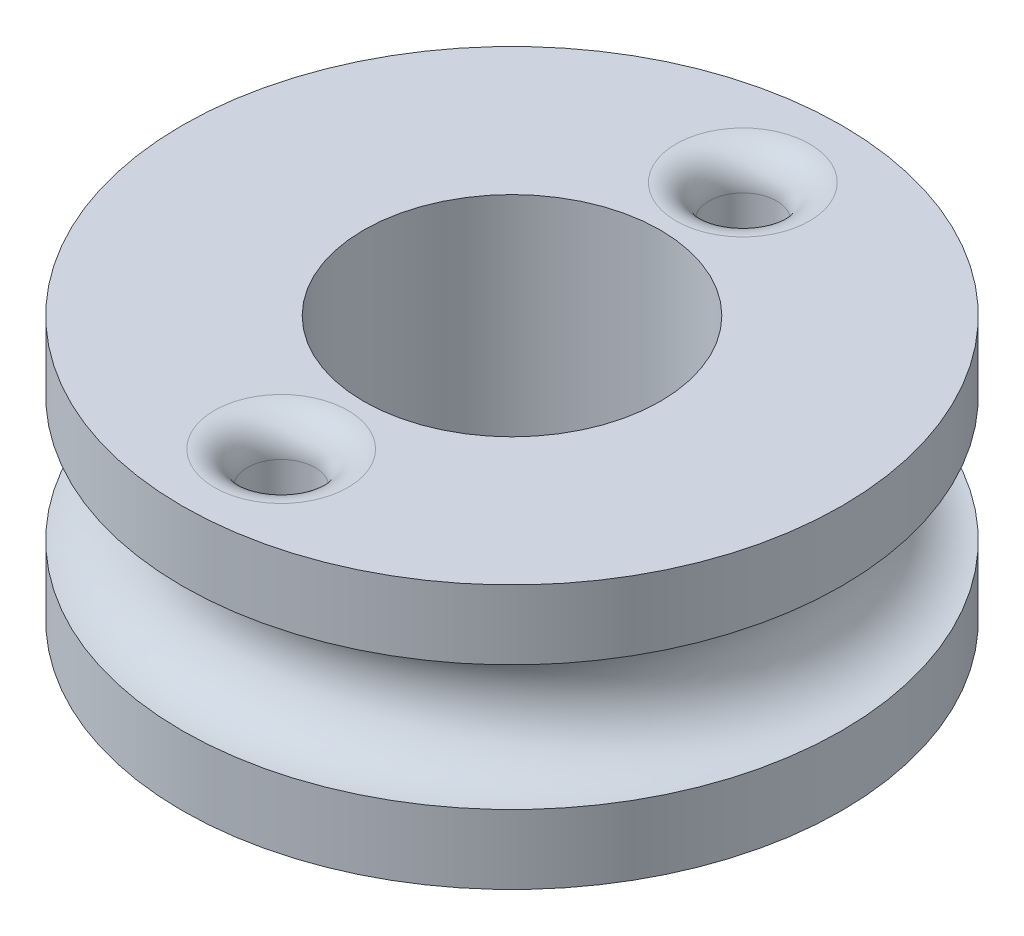
SolidWorks part; units mm, degrees
ref_plane "Front Plane" through (0, 0, 0) normal (0, 0, 1) x (1, 0, 0)
ref_plane "Top Plane" through (0, 0, 0) normal (0, 1, 0) x (1, 0, 0)
ref_plane "Right Plane" through (0, 0, 0) normal (1, 0, 0) x (0, 0, -1)
sketch "Sketch1" plane through (0, 0, 0) normal (0, 1, 0) x (1, 0, 0)
  circle A0 centre (0, 0) radius 10
  circle A1 centre (0, 0) radius 4.5
  dimension "D1" = 20
  dimension "D2" = 9
extrude "Boss-Extrude1" add sketch "Sketch1" along normal blind 8
sketch "Sketch3" plane through (0, 0, 0) normal (0, 0, 1) x (1, 0, 0)
  line L0 (0, -0.9519) -> (0, 8.8261) construction
  line L1 (-17.7863, 4) -> (10.4979, 4) construction
  line L2 (-10, 8) -> (-10, 0) construction
  circle A0 centre (-10, 4) radius 1.9
  point P5 (-10, 4)
  dimension "D1" = 3.8
revolve "Cut-Revolve1" cut sketch "Sketch3" angle 360 about L0
sketch "Sketch4" plane through (0, 0, 0) normal (0, 1, 0) x (1, 0, 0)
  line L0 (0, -10.4421) -> (0, 10.5997) construction
  line L1 (-11.1514, 0) -> (12.964, 0) construction
  circle A0 centre (0, 7) radius 1.025
  circle A1 centre (0, 0) radius 10 construction
  circle A2 centre (0, -7) radius 1.025
  point P9 (0, 10)
  dimension "D1" = 2.05
  dimension "D2" = 3
extrude "Cut-Extrude1" cut sketch "Sketch4" along normal blind 8 contours A0 | A2
sketch "Sketch5" plane through (0, 0, 0) normal (0, 1, 0) x (1, 0, 0)
  line L0 (-11.6439, 0) -> (11.8606, 0) construction
  line L1 (0.6305, 8.025) -> (-0.6305, 8.025)
  line L2 (0.6305, 8.025) -> (0.6305, 10)
  line L3 (0.6305, 10) -> (-0.6305, 10)
  line L4 (-0.6305, 8.025) -> (-0.6305, 10)
  line L5 (0.6305, 8.025) -> (-0.6305, 10) construction
  line L6 (0.6305, 10) -> (-0.6305, 8.025) construction
  line L7 (0.6305, -10) -> (-0.6305, -8.025) construction
  line L8 (0.6305, -8.025) -> (-0.6305, -10) construction
  line L9 (0.6305, -10) -> (-0.6305, -10)
  line L10 (0.6305, -8.025) -> (0.6305, -10)
  line L11 (0.6305, -8.025) -> (-0.6305, -8.025)
  line L12 (-0.6305, -8.025) -> (-0.6305, -10)
  circle A0 centre (0, 0) radius 10 construction
  circle A1 centre (0, 7) radius 1.025 construction
  point P0 (0, 9.0125)
extrude "Boss-Extrude3" [suppressed] add sketch "Sketch5" along normal blind 8 contours L4 L1 L2 L3 | L9 L12 L11 L10
fillet "Fillet1" [suppressed] radius 1
fillet "Fillet3" radius 1 2 edges at (0, 8, -5.975) (0, 8, 5.975)
